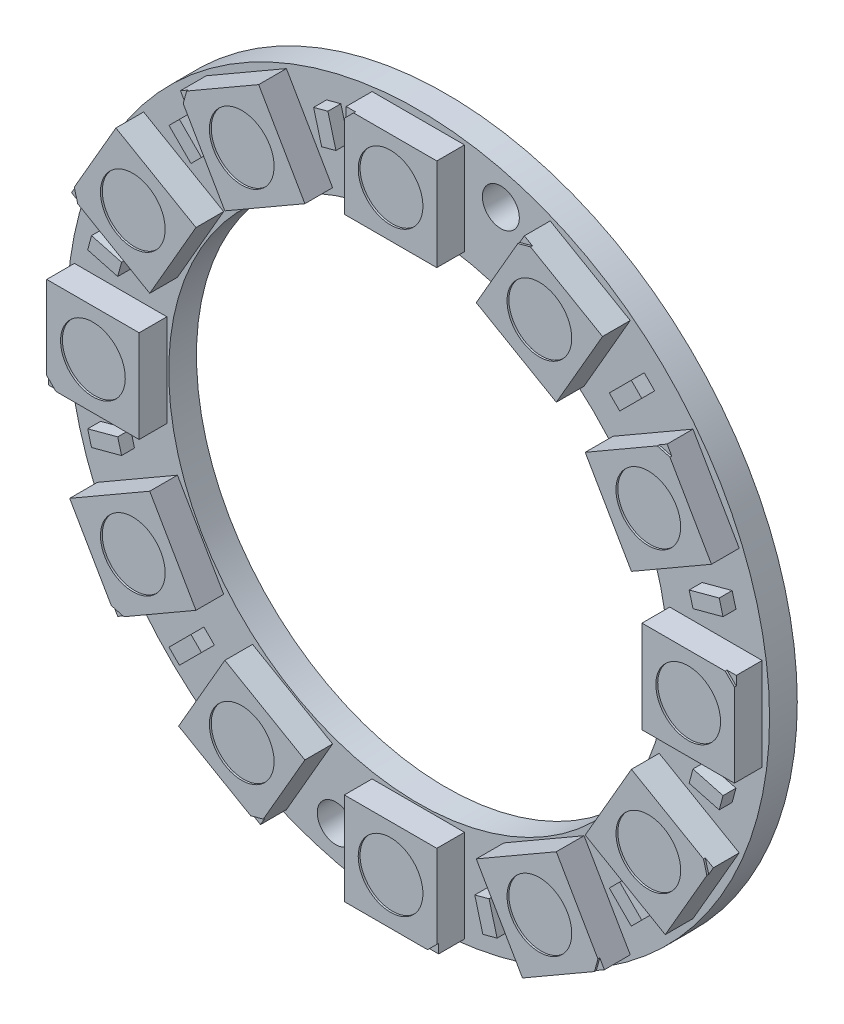
SolidWorks part; units mm, degrees
note: '?' marks a value the reader was unsure of.
ref_plane "正面" through (0, 0, 0) normal (0, 0, 1) x (1, 0, 0)
ref_plane "平面" through (0, 0, 0) normal (0, 1, 0) x (1, 0, 0)
ref_plane "右側面" through (0, 0, 0) normal (1, 0, 0) x (0, 0, -1)
sketch "ｽｹｯﾁ1" plane through (0, 0, 0) normal (0, 0, 1) x (1, 0, 0)
  circle A0 centre (0, 0) radius 19
  circle A1 centre (0, 0) radius 13.5
  dimension "D1" = 38
  dimension "D2" = 27
extrude "ﾎﾞｽ - 押し出し1" add sketch "ｽｹｯﾁ1" along normal blind 1.5
sketch "ｽｹｯﾁ2" plane through (0, 0, 1.5) normal (0, 0, 1) x (1, 0, 0)
  line L1 (-2.5, 18.6) -> (2.5, 18.6)
  line L2 (-2.5, 18.6) -> (-2.5, 13.6)
  line L3 (-2.5, 13.6) -> (2.5, 13.6)
  line L4 (2.5, 18.6) -> (2.5, 13.6)
  point P4 (0, 13.6)
  dimension "D1" = 0
  dimension "D2" = 13.6
  dimension "D3" = 5
  dimension "D4" = 5
extrude "ﾎﾞｽ - 押し出し2" add sketch "ｽｹｯﾁ2" along normal blind 1.5
ref_axis "軸1" through (0, 0, 1.5) along (0, 0, -1)?
pattern_circular "円形ﾊﾟﾀｰﾝ2" count 12 over 360 about axis through (0, 0, 0) along (0, 0, 1) of "ﾎﾞｽ - 押し出し2"
sketch "ｽｹｯﾁ6" plane through (0, 0, 3) normal (0, 0, 1) x (1, 0, 0)
  line L0 (2.5, 13.6) -> (2.5, 18.6) construction
  line L1 (2.5, 18.6) -> (-2.5, 18.6) construction
  line L2 (-2.5, 18.1) -> (-2, 18.6)
  line L3 (-2.5, 18.6) -> (-2.5, 13.6) construction
  line L4 (2.5, 18.6) -> (-2.5, 18.6) construction
  line L5 (-2, 18.6) -> (-2.5, 18.6)
  line L6 (-2.5, 18.6) -> (-2.5, 18.1)
  circle A0 centre (0, 16.1) radius 1.75
  point P4 (2.5, 16.1)
  point P7 (0, 18.6)
  dimension "D1" = 3.5
  dimension "D2" = 2.5
  dimension "D3" = 2.5
  dimension "D4" = 0.5
  dimension "D5" = 0.5
extrude "ｶｯﾄ - 押し出し1" cut sketch "ｽｹｯﾁ6" against normal blind 0.1
pattern_circular "円形ﾊﾟﾀｰﾝ3" count 12 over 360 about axis through (0, 0, 0) along (0, 0, 1) of "ｶｯﾄ - 押し出し1"
sketch "ｽｹｯﾁ7" plane through (0, 0, 0) normal (0, 0, -1) x (-1, 0, 0)
  line L0 (0, 0) -> (0, 19) construction
  circle A0 centre (4.4646, -16.6622) radius 1
  circle A1 centre (-4.4646, 16.6622) radius 1
  circle A2 centre (0, 0) radius 19 construction
  dimension "D1" = 34.5
  dimension "D3" = 2
  dimension "D4" = 2
  dimension "D2" = 17.25
  dimension "D5" = 15
  dimension "D6" = 180
extrude "ｶｯﾄ - 押し出し2" cut sketch "ｽｹｯﾁ7" against normal through all
sketch "ｽｹｯﾁ8" plane through (0, 0, 1.5) normal (0, 0, 1) x (1, 0, 0)
  line L0 (4.5275, -15.3513) -> (3.7547, -15.5583)
  line L1 (4.5275, -15.3513) -> (4.9629, -16.9764)
  line L2 (3.7547, -15.5583) -> (4.1902, -17.1835)
  line L3 (4.9629, -16.9764) -> (4.1902, -17.1835)
  line L4 (0, 0) -> (0, -13.5) construction
  line L5 (4.5766, -17.08) -> (0, 0) construction
  circle A0 centre (0, 0) radius 13.5 construction
  point P11 (4.1411, -15.4548)
  dimension "D1" = 0.8
  dimension "D2" = 1.6825
  dimension "D3" = 15
  dimension "D4" = 16
extrude "ﾎﾞｽ - 押し出し3" add sketch "ｽｹｯﾁ8" along normal blind 0.7
pattern_circular "円形ﾊﾟﾀｰﾝ4" count 5 every 30 about axis through (0, 0, 0) along (0, 0, 1) of "ﾎﾞｽ - 押し出し3"
pattern_circular "円形ﾊﾟﾀｰﾝ5" count 2 every 60 about axis through (0, 0, 0) along (0, 0, 1) of "ﾎﾞｽ - 押し出し3"
pattern_circular "円形ﾊﾟﾀｰﾝ6" count 5 every 30 about axis through (0, 0, 1.5) along (0, 0, -1) skipping 1 of "円形ﾊﾟﾀｰﾝ5", "ﾎﾞｽ - 押し出し3"
